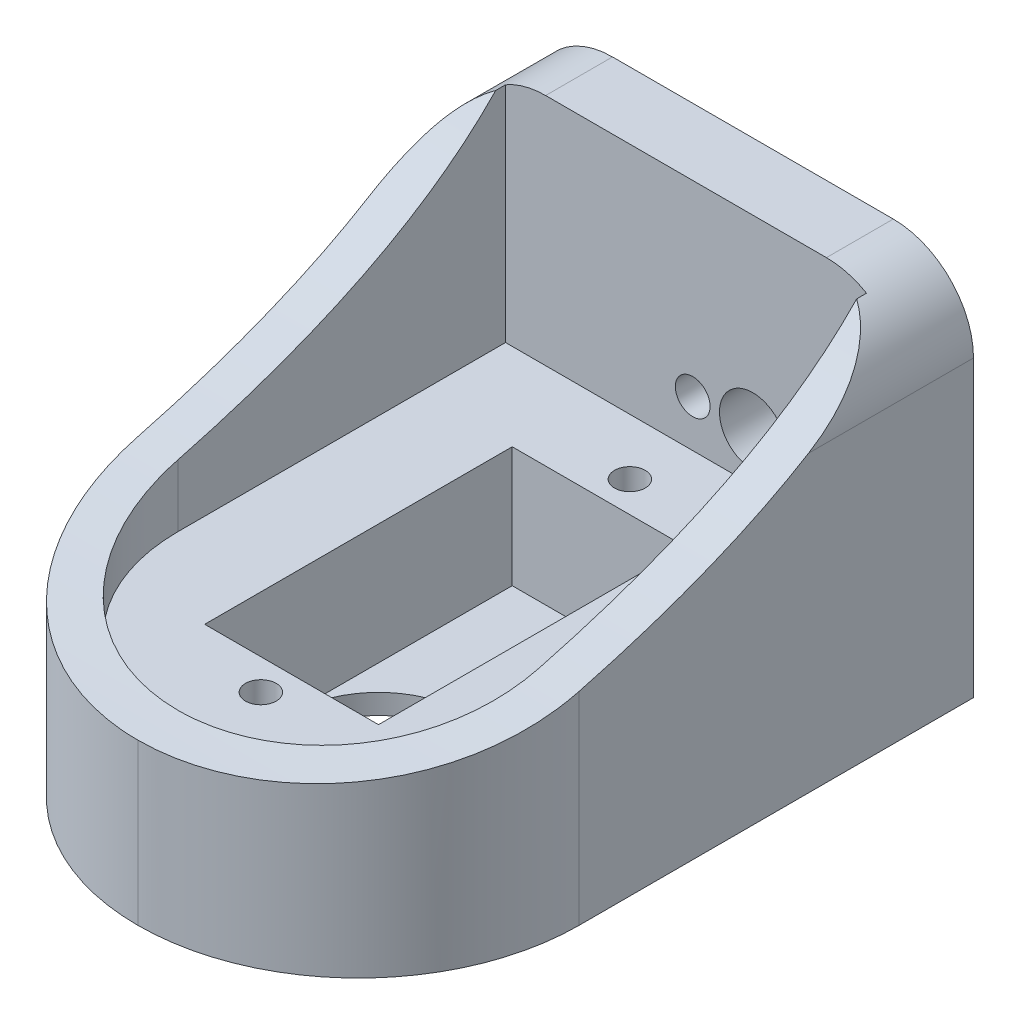
SolidWorks part; units mm, degrees
material "Cast Alloy Steel"
ref_plane "Front Plane" through (0, 0, 0) normal (0, 0, 1) x (1, 0, 0)
ref_plane "Top Plane" through (0, 0, 0) normal (0, 1, 0) x (1, 0, 0)
ref_plane "Right Plane" through (0, 0, 0) normal (1, 0, 0) x (0, 0, -1)
sketch "Sketch2" plane through (0, 0, 0) normal (0, 0, 1) x (1, 0, 0)
  line L1 (-16.5, 14) -> (16.5, 14)
  line L2 (-16.5, 14) -> (-16.5, -14)
  line L3 (-16.5, -14) -> (16.5, -14)
  line L4 (16.5, 14) -> (16.5, -14)
  line L5 (-16.5, 14) -> (16.5, -14) construction
  line L6 (-16.5, -14) -> (16.5, 14) construction
  point P0 (0, 0)
  dimension "D1" = 33
  dimension "D2" = 28
extrude "Boss-Extrude1" add sketch "Sketch2" along normal blind 46
sketch "Sketch3" plane through (-16.5, 0, 0) normal (-1, 0, 0) x (0, 0, 1)
  line L0 (46, 14) -> (46, -14) construction
  line L1 (5, 14) -> (46, 14)
  line L2 (5, 14) -> (5, -3.5)
  line L3 (5, -3.5) -> (46, -3.5)
  line L4 (46, 14) -> (46, -3.5)
  line L5 (0, 14) -> (0, -14) construction
  line L6 (46, -14) -> (0, -14) construction
  line L7 (46, 14) -> (0, 14) construction
  dimension "D1" = 5
  dimension "D2" = 10.5
extrude "Cut-Extrude1" cut sketch "Sketch3" against normal through all both
sketch "Sketch4" plane through (-16.5, 0, 0) normal (-1, 0, 0) x (0, 0, 1)
  line L0 (46, -2) -> (46, -3.5)
  line L1 (5, 14) -> (5, -3.5)
  line L2 (5, -3.5) -> (46, -3.5)
  spline S0 degree 2 poles (5, 14) (15.4322, 2.1011) (46, -2) knots 0 0 0 1 1 1
  dimension "D1" = 1.5
extrude "Boss-Extrude2" add sketch "Sketch4" against normal blind 3
mirror "Mirror1" about plane through (0, 0, 0) normal (1, 0, 0) of "Boss-Extrude2"
sketch "Sketch5" plane through (-13.5, 0, 0) normal (1, 0, 0) x (0, 0, -1)
  line L0 (-43, -3.5) -> (-43, -1.5714)
  line L3 (-46, -2) -> (-46, -3.5)
  line L4 (-46, -3.5) -> (-5, -3.5)
  line L5 (-5, -3.5) -> (-5, 14)
  line L6 (-46, -2) -> (-46, -3.5)
  line L7 (-46, -3.5) -> (-5, -3.5)
  line L8 (-5, -3.5) -> (-5, 14)
  parabola Q1 (-5, 14) -> (-46, -2) focus (-10.5666, 24.1739) apex (-1.0259, 20.4792)
  parabola Q2 (-5, 14) -> (-46, -2) focus (-10.5666, 24.1739) apex (-1.0259, 20.4792)
  spline M6 degree 2 poles (-46, -2) (-15.4322, 2.1011) (-5, 14) knots 0 0 0 1 1 1
  line M7 (-46, -2) -> (-46, -3.5)
  line M8 (-46, -3.5) -> (-5, -3.5)
  dimension "D2" = 3
  dimension "D1" = 0
extrude "Boss-Extrude3" add sketch "Sketch5" along normal up to surface (27 mm away) contours L0 M8 M6 M7 region at (-13.5, -2.6406, 44.4373) up to face at (13.5, 1.4375, 30.625)
fillet "Fillet2" radius 13.5 2 edges
fillet "Fillet3" radius 16.5 2 edges at (-16.5, -8, 46) (16.5, -8, 46)
fillet "Fillet4" radius 6 2 edges at (-16.5, 14, 2.5) (16.5, 14, 2.5)
sketch "Sketch6" plane through (0, -3.5, 0) normal (0, 1, 0) x (1, 0, 0)
  line L0 (13.5, -5) -> (-13.5, -5) construction
  line L1 (-6.5, -11.5) -> (6.5, -11.5)
  line L2 (-6.5, -11.5) -> (-6.5, -34.5)
  line L3 (-6.5, -34.5) -> (6.5, -34.5)
  line L4 (6.5, -11.5) -> (6.5, -34.5)
  point P6 (0, -34.5)
  dimension "D1" = 23
  dimension "D2" = 13
  dimension "D3" = 6.5
extrude "Cut-Extrude2" cut sketch "Sketch6" against normal blind 9
sketch "Sketch7" plane through (0, -12.5, 0) normal (0, 1, 0) x (1, 0, 0)
  line L1 (-6.5, -34.5) -> (6.5, -34.5) construction
  circle A0 centre (0, -28) radius 6.5
  dimension "D1" = 13
  dimension "D2" = 6.5
extrude "Cut-Extrude3" cut sketch "Sketch7" against normal blind 9
sketch "Sketch8" plane through (0, -3.5, 0) normal (0, 1, 0) x (1, 0, 0)
  line L0 (0, -34.5) -> (6.5, -34.5) construction
  circle A0 centre (0, -9.2) radius 1.15
  circle A1 centre (0, -36.8) radius 1.15
  dimension "D1" = 2.3
  dimension "D2" = 27.6
  dimension "D3" = 2.3
extrude "Cut-Extrude4" cut sketch "Sketch8" against normal blind 8
sketch "Sketch9" plane through (0, 0, 5) normal (0, 0, 1) x (1, 0, 0)
  line L1 (16.5, 1.155) -> (16.5, -14) construction
  circle A0 centre (0.5, 0) radius 1.3
  circle A1 centre (5, 0) radius 2.5
  circle A2 centre (9.5, 0) radius 1.3
  dimension "D1" = 2.6
  dimension "D2" = 2.6
  dimension "D3" = 5
  dimension "D4" = 4.5
  dimension "D5" = 9
  dimension "D6" = 11.5
extrude "Cut-Extrude5" cut sketch "Sketch9" against normal through all
